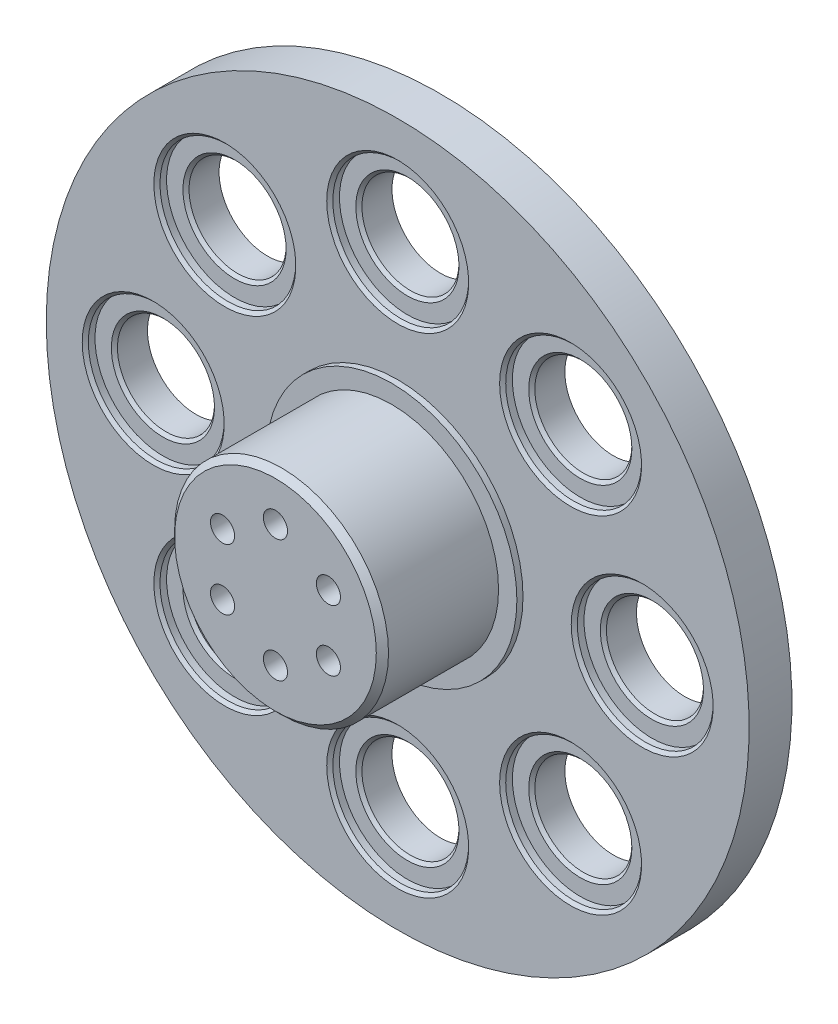
SolidWorks part; units mm, degrees
material "PETG"
ref_plane "Front Plane" through (0, 0, 0) normal (0, 0, 1) x (1, 0, 0)
ref_plane "Top Plane" through (0, 0, 0) normal (0, 1, 0) x (1, 0, 0)
ref_plane "Right Plane" through (0, 0, 0) normal (1, 0, 0) x (0, 0, -1)
sketch "Sketch1" plane through (0, 0, 0) normal (0, 0, 1) x (1, 0, 0)
  circle A0 centre (0, 0) radius 17.5
  dimension "D1" = 35
extrude "Boss-Extrude1" add sketch "Sketch1" along normal blind 19
sketch "Sketch7" plane through (0, 0, 0) normal (0, 0, -1) x (-1, 0, 0)
  circle A0 centre (0, 0) radius 20.5
  dimension "D1" = 41
extrude "Boss-Extrude3" add sketch "Sketch7" along normal blind 1
sketch "Sketch3" plane through (0, 0, -1) normal (0, 0, -1) x (-1, 0, 0)
  circle A0 centre (0, 0) radius 57.5
  dimension "D1" = 115
extrude "Boss-Extrude2" add sketch "Sketch3" along normal blind 7
sketch "Sketch4" plane through (0, 0, -8) normal (0, 0, -1) x (-1, 0, 0)
  circle A0 centre (0, 0) radius 11
  dimension "D1" = 22
extrude "Cut-Extrude1" cut sketch "Sketch4" against normal blind 7
sketch "Sketch5" plane through (0, 0, -1) normal (0, 0, -1) x (-1, 0, 0)
  circle A0 centre (0, 0) radius 7.5
  dimension "D1" = 15
extrude "Cut-Extrude2" cut sketch "Sketch5" against normal blind 0.5
sketch "Sketch6" plane through (0, 0, 19) normal (0, 0, 1) x (1, 0, 0)
  circle A0 centre (0, 10) radius 1.975
  dimension "D1" = 3.95
  dimension "D2" = 10
extrude "Cut-Extrude3" cut sketch "Sketch6" against normal blind 10
pattern_circular "CirPattern1" count 6 over 360 about axis through (0, 0, 19) along (0, 0, 1) of "Cut-Extrude3"
chamfer "Chamfer1" distance 1 angle 45 2 edges at (-11, 0, -8) (17.5, 0, 19)
sketch "Sketch8" plane through (0, 0, -1) normal (0, 0, 1) x (1, 0, 0)
  circle A0 centre (0, 0) radius 40 construction
  circle A1 centre (-40, 0) radius 7.94
  circle A2 centre (-28.2843, 28.2843) radius 7.94
  circle A3 centre (0, 40) radius 7.94
  circle A4 centre (28.2843, 28.2843) radius 7.94
  circle A5 centre (40, 0) radius 7.94
  circle A6 centre (28.2843, -28.2843) radius 7.94
  circle A7 centre (0, -40) radius 7.94
  circle A8 centre (-28.2843, -28.2843) radius 7.94
  dimension "D1" = 80
  dimension "D2" = 15.88
  dimension "D3" = 8
extrude "Cut-Extrude4" cut sketch "Sketch8" against normal through all
sketch "Sketch9" plane through (0, 0, -1) normal (0, 0, 1) x (1, 0, 0)
  line L0 (0, 0) -> (0, 40) construction
  circle A0 centre (0, 40) radius 11.1125
  circle A1 centre (0, 40) radius 7.94 construction
  circle A2 centre (28.2843, 28.2843) radius 11.1125
  circle A3 centre (40, 0) radius 11.1125
  circle A4 centre (28.2843, -28.2843) radius 11.1125
  circle A5 centre (0, -40) radius 11.1125
  circle A6 centre (-28.2843, -28.2843) radius 11.1125
  circle A7 centre (-40, 0) radius 11.1125
  circle A8 centre (-28.2843, 28.2843) radius 11.1125
  point P17 (0, 0)
  dimension "D1" = 22.225
  dimension "D2" = 8
extrude "Cut-Extrude5" cut sketch "Sketch9" against normal blind 1.5875
chamfer "Chamfer2" distance 0.5 angle 45 8 edges at (-32.06, 0, -2.5875) (-20.3443, -28.2843, -2.5875) (7.94, -40, -2.5875) (36.2243, -28.2843, -2.5875) (47.94, 0, -2.5875) (36.2243, 28.2843, -2.5875) (-20.3443, 28.2843, -2.5875) (7.94, 40, -2.5875)
chamfer "Chamfer3" distance 0.5 angle 45 8 edges at (-17.1718, 28.2843, -1) (-28.8875, 0, -1) (-17.1718, -28.2843, -1) (11.1125, -40, -1) (39.3968, -28.2843, -1) (51.1125, 0, -1) (39.3968, 28.2843, -1) (11.1125, 40, -1)
sketch "Sketch10" [suppressed] plane through (0, 0, -1) normal (0, 0, 1) x (1, 0, 0)
  line L0 (0, 0) -> (0, 40) construction
  circle A0 centre (0, 40) radius 6.35
  circle A1 centre (0, 0) radius 40 construction
  circle A2 centre (28.2843, 28.2843) radius 6.35
  circle A3 centre (40, 0) radius 6.35
  circle A4 centre (28.2843, -28.2843) radius 6.35
  circle A5 centre (0, -40) radius 6.35
  circle A6 centre (-28.2843, -28.2843) radius 6.35
  circle A7 centre (-40, 0) radius 6.35
  circle A8 centre (-28.2843, 28.2843) radius 6.35
  dimension "D1" = 80
  dimension "D3" = 8
  dimension "D2" = 12.7
extrude "Cut-Extrude6" [suppressed] cut sketch "Sketch10" against normal through all
chamfer "Chamfer4" [suppressed] distance 0.5 angle 45
equation "\"N\"= 21"
equation "\"R\"= 65mm"
equation "\"E\" = ROUND(\"R\" / \"N\" * 0.7, 2)"
equation "\"R_r\" = ( 1in / 2 ) / 2"
equation "\"D_p\" = 8cm"
equation "\"D1@Sketch8\"=\"D_p\""
equation "\"N_p\" = 8"
equation "\"D3@Sketch8\"=\"N_p\""
equation "\"D1@Sketch10\"=\"D_p\""
equation "\"D3@Sketch10\"=\"N_p\""
equation "\"D2@Sketch10\"=\"R_r\"*2"
